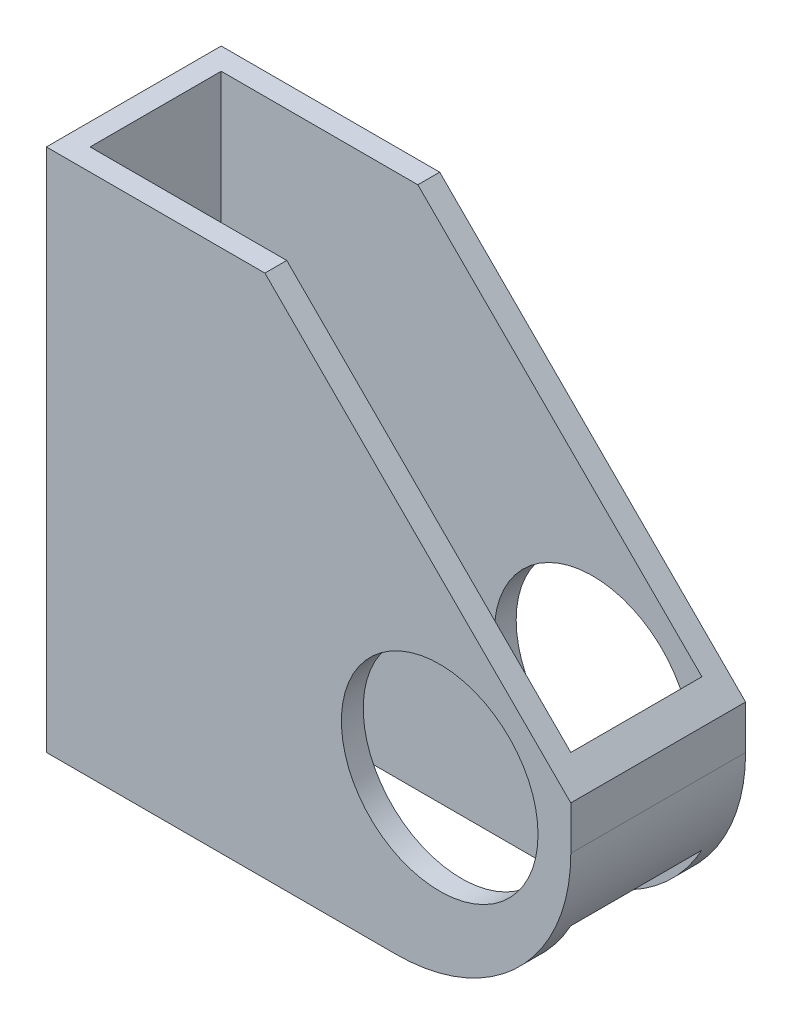
SolidWorks part; units mm, degrees
ref_plane "Front Plane" through (0, 0, 0) normal (0, 0, 1) x (1, 0, 0)
ref_plane "Top Plane" through (0, 0, 0) normal (0, 1, 0) x (1, 0, 0)
ref_plane "Right Plane" through (0, 0, 0) normal (1, 0, 0) x (0, 0, -1)
sketch "Sketch1" plane through (0, 0, 0) normal (0, 0, 1) x (1, 0, 0)
  line L1 (-38.1, 38.1) -> (38.1, 38.1)
  line L2 (-38.1, 38.1) -> (-38.1, -38.1)
  line L3 (-38.1, -38.1) -> (38.1, -38.1)
  line L4 (38.1, 38.1) -> (38.1, -38.1)
  line L5 (-38.1, 38.1) -> (38.1, -38.1) construction
  line L6 (-38.1, -38.1) -> (38.1, 38.1) construction
  circle A0 centre (19.05, -12.7) radius 14.2875
  point P0 (0, 0)
  dimension "D3" = 57.15
  dimension "D4" = 25.4
  dimension "D5" = 28.575
  dimension "D1" = 76.2
  dimension "D2" = 76.2
extrude "Boss-Extrude1" add sketch "Sketch1" along normal mid plane 25.4
hole_wizard "1/4 (0.25) Diameter Hole1" positions "Sketch5" profile "Sketch6" hole size "1/4" standard "ANSI Inch"
sketch "Sketch5" plane through (-38.1, 0, 0) normal (-1, 0, 0) x (0, 0, 1)
  line L0 (12.7, -38.1) -> (-12.7, -38.1) construction
  point P0 (0, -9.525)
  point P2 (0, -28.575)
  dimension "D1" = 9.525
  dimension "D2" = 19.05
sketch "Sketch6" plane through (-38.1, -9.525, 0) normal (0, 1, 0) x (0, 0, 1)
  line L0 (0, 0) -> (0, 6.9877)
  line L1 (0, 6.9877) -> (3.175, 5.08)
  line L2 (3.175, 5.08) -> (3.175, 0)
  line L5 (3.175, 0) -> (0, 0)
  line L10 (0, 6.9877) -> (-3.175, 5.08) construction
  line L11 (0, -6.35) -> (0, 107.95) construction
  dimension "Hole Dia." = 6.35
  dimension "Hole Depth" = 5.08
  dimension "Drill Angle" = 118
chamfer "Chamfer1" distance 44.45 angle 45 1 edges at (38.1, 38.1, 0)
sketch "Sketch7" plane through (0, -38.1, 0) normal (0, -1, 0) x (1, 0, 0)
  line L8 (-34.925, -9.525) -> (34.925, -9.525)
  line L9 (34.925, -9.525) -> (34.925, 9.525)
  line L10 (34.925, 9.525) -> (-34.925, 9.525)
  line L11 (-34.925, 9.525) -> (-34.925, -9.525)
  line L12 (-34.925, -9.525) -> (34.925, -9.525)
  line L13 (34.925, -9.525) -> (34.925, 9.525)
  line L14 (34.925, 9.525) -> (-34.925, 9.525)
  line L15 (-34.925, 9.525) -> (-34.925, -9.525)
  dimension "D1" = 3.175
extrude "Cut-Extrude1" cut sketch "Sketch7" against normal through all
fillet "Fillet1" radius 25.4 1 edges at (38.1, -38.1, 0)
